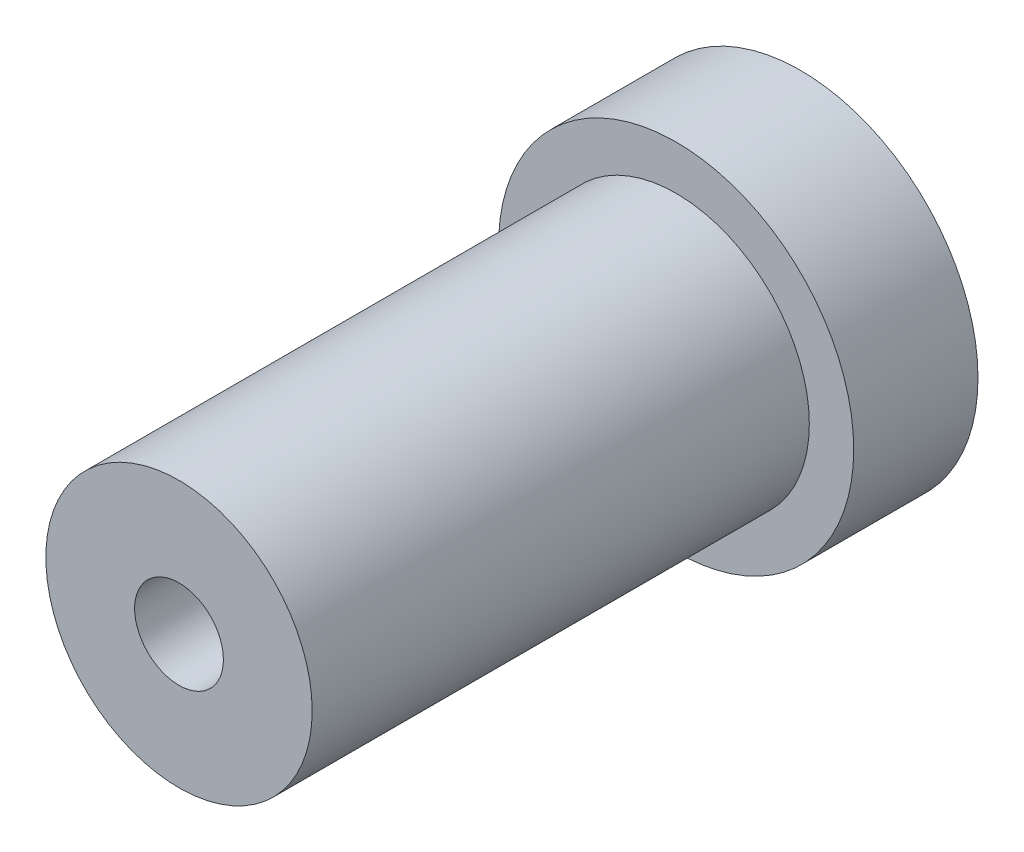
SolidWorks part; units mm, degrees
ref_plane "Front Plane" through (0, 0, 0) normal (0, 0, 1) x (1, 0, 0)
ref_plane "Top Plane" through (0, 0, 0) normal (0, 1, 0) x (1, 0, 0)
ref_plane "Right Plane" through (0, 0, 0) normal (1, 0, 0) x (0, 0, -1)
sketch "Sketch1" plane through (0, 0, 0) normal (0, 0, 1) x (1, 0, 0)
  circle A0 centre (-20, 10) radius 1
  circle A1 centre (-20, 10) radius 4
  dimension "D1" = 2
  dimension "D2" = 8
extrude "Boss-Extrude1" add sketch "Sketch1" along normal blind 2.8
cosmetic thread "Cosmetic Thread1" parameters "D2"=2.5
cosmetic thread "Cosmetic Thread2" parameters "D1"=5, "D2"=2.5
sketch "Sketch2" plane through (0, 0, 2.8) normal (0, 0, 1) x (1, 0, 0)
  circle A0 centre (-20, 10) radius 1
  circle A1 centre (-20, 10) radius 3
  dimension "D1" = 2
  dimension "D2" = 6
extrude "Boss-Extrude2" add sketch "Sketch2" along normal blind 11.2
ref_axis "Axis1" through (-20, 10, 14) along (0, 0, -1)
